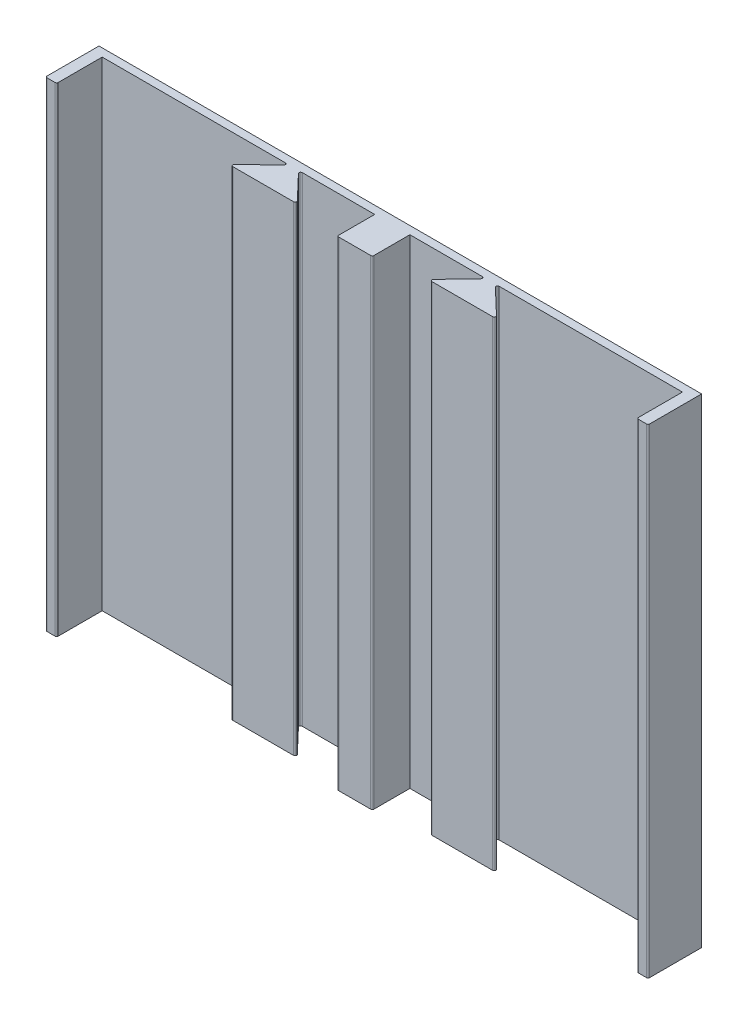
SolidWorks part; units mm, degrees
ref_plane "Front Plane" through (0, 0, 0) normal (0, 0, 1) x (1, 0, 0)
ref_plane "Top Plane" through (0, 0, 0) normal (0, 1, 0) x (1, 0, 0)
ref_plane "Right Plane" through (0, 0, 0) normal (1, 0, 0) x (0, 0, -1)
sketch "Sketch1" plane through (0, 0, 0) normal (0, 1, 0) x (1, 0, 0)
  line L0 (21.037, 4.7814) -> (21.037, 3.7814) construction
  line L2 (7.721, 3.7814) -> (3.537, -0.2186)
  line L3 (3.537, -0.2186) -> (13.537, -0.2186)
  line L4 (9.721, 3.7814) -> (13.537, -0.2186)
  line L5 (-14.963, 3.7814) -> (7.721, 3.7814)
  line L6 (-16.963, 3.7814) -> (-16.963, 4.7814)
  line L7 (-16.963, 4.7814) -> (59.037, 4.7814)
  line L8 (59.037, 3.7814) -> (59.037, 4.7814)
  line L9 (38.537, -0.2186) -> (28.537, -0.2186)
  line L10 (32.353, 3.7814) -> (28.537, -0.2186)
  line L12 (34.353, 3.7814) -> (38.537, -0.2186)
  line L13 (9.721, 3.7814) -> (18.537, 3.7814)
  line L14 (34.353, 3.7814) -> (57.037, 3.7814)
  line L15 (57.037, -2.2186) -> (59.037, -2.2186)
  line L17 (-14.963, 3.7814) -> (-14.963, -2.2186)
  line L18 (-14.963, -2.2186) -> (-16.963, -2.2186)
  line L19 (-16.963, 3.7814) -> (-16.963, -2.2186)
  line L20 (59.037, 3.7814) -> (59.037, -2.2186)
  line L22 (57.037, 3.7814) -> (57.037, -2.2186)
  line L23 (23.537, 3.7814) -> (32.353, 3.7814)
  line L25 (23.537, 3.7814) -> (23.537, -1.2186)
  line L26 (23.537, -1.2186) -> (18.537, -1.2186)
  line L27 (18.537, 3.7814) -> (18.537, -1.2186)
  point P14 (8.537, -0.2186)
  point P15 (33.537, -0.2186)
  point P26 (21.037, -1.2186)
  dimension "D1" = 10
  dimension "D2" = 6
  dimension "D3" = 2
  dimension "D4" = 1
  dimension "D5" = 76
  dimension "D6" = 1
  dimension "D7" = 25
  dimension "D8" = 5
  dimension "D9" = 5
extrude "Boss-Extrude1" add sketch "Sketch1" along normal blind 60
other "Move Face1" flip direction yes face at (23.537, 30, -1.2814) face at (21.037, 30, 1.2186) face at (18.537, 30, -1.2814) face at (-16.963, 30, -1.2814) face at (-15.963, 30, 2.2186) face at (-14.963, 30, -0.7814) face at (5.629, 30, -1.7814) face at (30.445, 30, -1.7814) face at (8.537, 30, 0.2186) face at (11.629, 30, -1.7814) face at (33.537, 30, 0.2186) face at (36.445, 30, -1.7814) face at (57.037, 30, -0.7814) face at (58.037, 30, 2.2186) face at (59.037, 30, -1.2814) offset 0.3 parameters "D1"=0.3
fillet "Fillet1" radius 0.2 14 edges at (-16.663, 30, 1.9186) (-15.263, 30, 1.9186) (57.337, 30, 1.9186) (58.737, 30, 1.9186) (33.9188, 30, -3.7814) (37.7891, 30, -0.0814) (32.7676, 30, -3.7814) (9.3064, 30, -3.7814) (29.2378, 30, -0.0814) (23.237, 30, 0.9186) (18.837, 30, 0.9186) (12.8362, 30, -0.0814) (8.1552, 30, -3.7814) (4.2849, 30, -0.0814)
